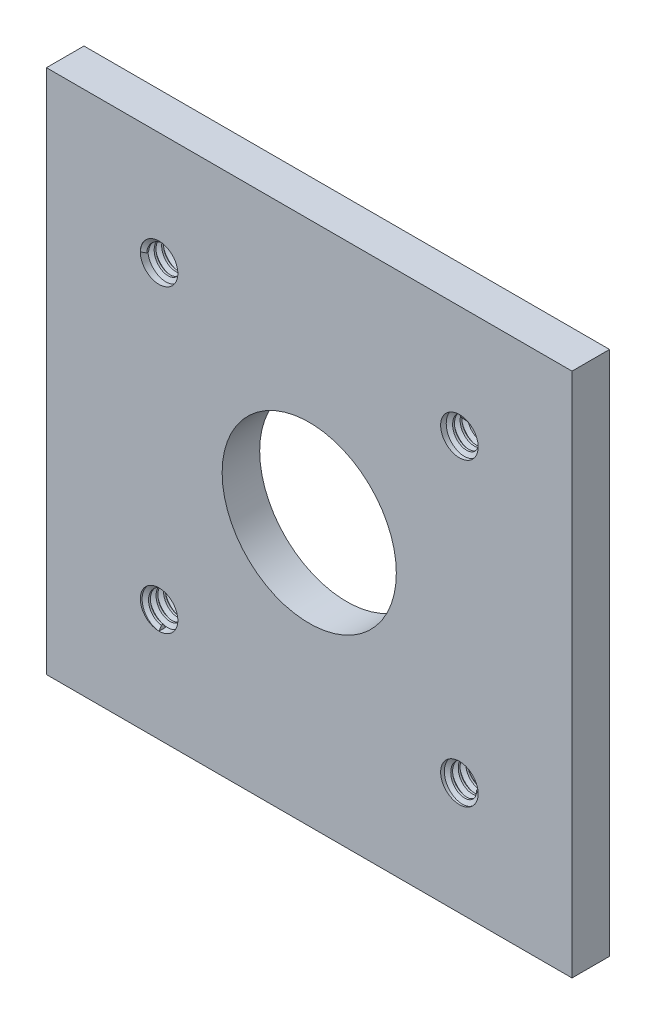
SolidWorks part; units mm, degrees
ref_plane "Front Plane" through (0, 0, 0) normal (0, 0, 1) x (1, 0, 0)
ref_plane "Top Plane" through (0, 0, 0) normal (0, 1, 0) x (1, 0, 0)
ref_plane "Right Plane" through (0, 0, 0) normal (1, 0, 0) x (0, 0, -1)
sketch "Sketch1" plane through (0, 0, 0) normal (0, 0, 1) x (1, 0, 0)
  line L1 (44.45, -44.45) -> (-44.45, -44.45)
  line L2 (44.45, -44.45) -> (44.45, 44.45)
  line L3 (44.45, 44.45) -> (-44.45, 44.45)
  line L4 (-44.45, -44.45) -> (-44.45, 44.45)
  line L6 (44.45, 44.45) -> (-44.45, -44.45) construction
  circle A0 centre (0, 0) radius 14.732
  circle A1 centre (-25.4, 25.4) radius 3.175
  circle A2 centre (25.4, 25.4) radius 3.175
  circle A3 centre (25.4, -25.4) radius 3.175
  circle A4 centre (-25.4, -25.4) radius 3.175
  point P0 (0, 0)
  dimension "D3" = 29.464
  dimension "D6" = 6.35
  dimension "D1" = 88.9
  dimension "D2" = 88.9
  dimension "D4" = 25.4
  dimension "D5" = 25.4
  dimension "D7" = 4
extrude "Boss-Extrude1" add sketch "Sketch1" along normal blind 6.35
thread "Thread1" pitch 1.27 method extrude profile "Thread Profile1" start angle 0, offset 0, length 6.35, pitch 1.27, diameter 6.35
ref_plane "Plane1" through (-28.575, 25.4, 6.35) normal (0, -1, 0) x (-1, 0, 0)
sketch "Thread Profile1" plane through (-28.575, 25.4, 6.35) normal (0, -1, 0) x (-1, 0, 0)
  line L0 (0, 0) -> (0, 1.27) construction
  line L11 (0, 0) -> (0, 1.1112)
  line L12 (0, 1.1112) -> (-0.6874, 0.7144)
  line L13 (-0.6874, 0.7144) -> (-0.6874, 0.3969)
  line L15 (-0.6874, 0.3969) -> (0, 0)
  line L17 (-0.6874, 0.5556) -> (0, 0.5556) construction
  point P2 (0, 0)
  dimension "Pitch" = 1.27
  dimension "Profile_Angle" = 60
  dimension "Profile_Land" = 0.3175
  dimension "Profile_Height" = 0.6874
pattern_circular "CirPattern1" count 4 over 360 about axis through (0, 0, 6.35) along (0, 0, 1) of "Thread1"
sketch "Sketch5" plane through (0, 0, 0) normal (0, 0, -1) x (-1, 0, 0)
  line L1 (44.45, -44.45) -> (-44.45, -44.45)
  line L2 (44.45, -44.45) -> (44.45, 44.45)
  line L3 (44.45, 44.45) -> (-44.45, 44.45)
  line L4 (-44.45, -44.45) -> (-44.45, 44.45)
  line L5 (44.45, -44.45) -> (-44.45, 44.45) construction
  line L6 (44.45, 44.45) -> (-44.45, -44.45) construction
  point P0 (0, 0)
extrude "Cut-Extrude1" cut sketch "Sketch5" along normal blind 6.35
